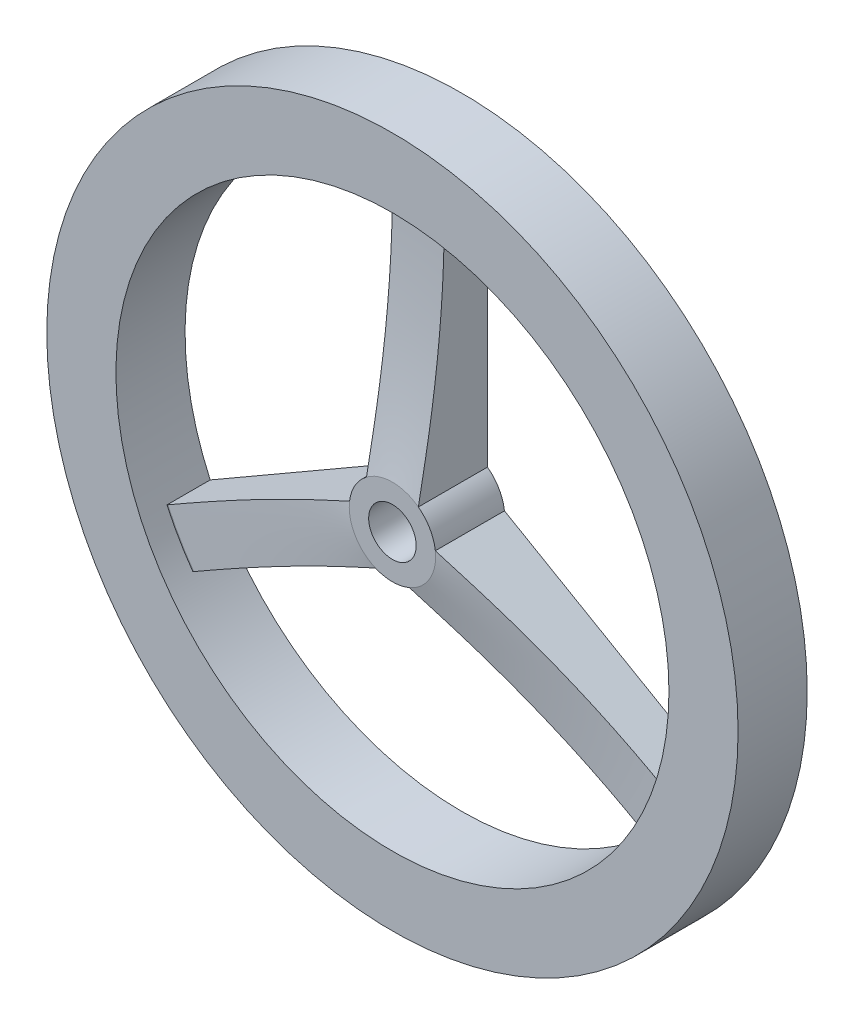
SolidWorks part; units mm, degrees
ref_plane "Front Plane" through (0, 0, 0) normal (0, 0, 1) x (1, 0, 0)
ref_plane "Top Plane" through (0, 0, 0) normal (0, 1, 0) x (1, 0, 0)
ref_plane "Right Plane" through (0, 0, 0) normal (1, 0, 0) x (0, 0, -1)
sketch "Sketch1" plane through (0, 0, 0) normal (0, 0, 1) x (1, 0, 0)
  line L0 (0, -32) -> (0, 32) construction
  line L1 (27.7128, -16) -> (-27.7128, 16) construction
  line L2 (-27.7128, -16) -> (27.7128, 16) construction
  line L3 (-3, 4) -> (-3, 31.8591)
  line L4 (3, 4) -> (3, 31.8591)
  line L5 (4.9641, 0.5981) -> (29.0908, -13.3315)
  line L6 (1.9641, -4.5981) -> (26.0908, -18.5276)
  line L7 (-1.9641, -4.5981) -> (-26.0908, -18.5276)
  line L8 (-4.9641, 0.5981) -> (-29.0908, -13.3315)
  circle A0 centre (0, 0) radius 40
  circle A1 centre (0, 0) radius 5
  circle A2 centre (0, 0) radius 32
  point P8 (0, 0)
  point P11 (0, 0)
  point P14 (0, 0)
  point P29 (0, 0)
  dimension "D1" = 80
  dimension "D2" = 8
  dimension "D3" = 10
  dimension "D4" = 60
  dimension "D5" = 60
  dimension "D6" = 3
  dimension "D7" = 3
extrude "Boss-Extrude1" add sketch "Sketch1" along normal mid plane 8 contours A0 A2 | L4 A2 L3 A1 | A1 | L6 A2 L5 A1 | L8 A2 L7 A1
sketch "Sketch3" plane through (0, 0, 4) normal (0, 0, 1) x (1, 0, 0)
  circle A0 centre (0, 0) radius 5
  circle A1 centre (0, 0) radius 32
  arc A2 (-3, 4) -> (-4.9641, 0.5981) centre (0, 0) ccw construction
  arc A3 (-3, 31.8591) -> (-29.0908, -13.3315) centre (0, 0) ccw construction
extrude "Cut-Extrude2" cut sketch "Sketch3" against normal blind 3
fillet "Fillet5" radius 122 3 edges at (4.3301, -2.5, 1) (-4.3301, -2.5, 1) (0, 5, 1)
sketch "Sketch12" plane through (0, 0, 4) normal (0, 0, 1) x (1, 0, 0)
  point P0 (0, 0)
hole_wizard "M5 Clearance Hole1" positions "Sketch13" profile "Sketch14" hole size "M5" standard "ANSI Metric" end condition through all
sketch "Sketch13" plane through (0, 0, 4) normal (0, 0, 1) x (1, 0, 0)
  point P0 (0, 0)
sketch "Sketch14" plane through (0, 0, 4) normal (1, 0, 0) x (0, -1, 0)
  line L0 (0, 0) -> (0, 8)
  line L1 (0, 8) -> (2.75, 8)
  line L2 (2.75, 8) -> (2.75, 0)
  line L5 (2.75, 0) -> (0, 0)
  line L11 (0, -6.35) -> (0, 107.95) construction
  dimension "Thru Hole Dia." = 5.5
  dimension "Thru Hole Depth" = 8
